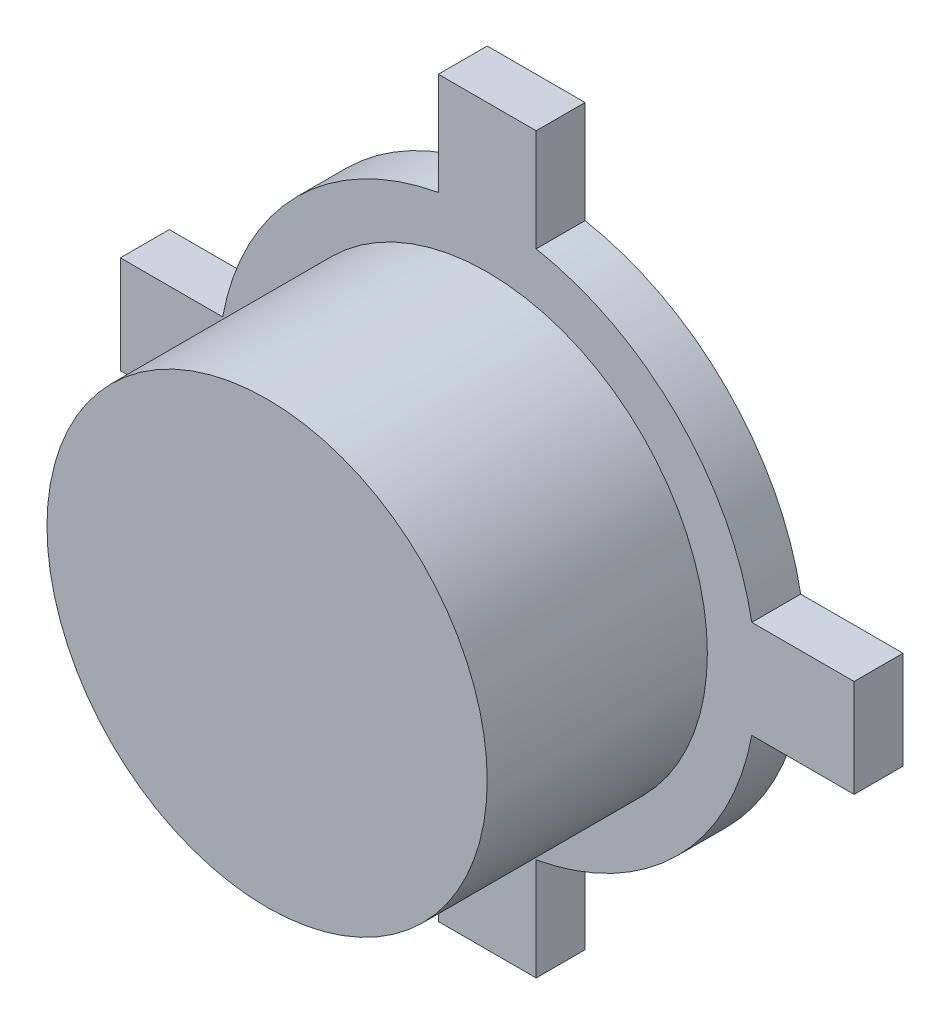
SolidWorks part; units mm, degrees
ref_plane "Front Plane" through (0, 0, 0) normal (0, 0, 1) x (1, 0, 0)
ref_plane "Top Plane" through (0, 0, 0) normal (0, 1, 0) x (1, 0, 0)
ref_plane "Right Plane" through (0, 0, 0) normal (1, 0, 0) x (0, 0, -1)
sketch "Sketch1" plane through (0, 0, 0) normal (0, 0, 1) x (1, 0, 0)
  circle A0 centre (0, 0) radius 4.5
  circle A1 centre (0, 0) radius 5 construction
  dimension "D1" = 0.5
extrude "Boss-Extrude1" add sketch "Sketch1" along normal blind 4.5
sketch "Sketch2" plane through (0, 0, 0) normal (0, 0, -1) x (-1, 0, 0)
  line L110 (-5.4083, 1) -> (-7.5, 1)
  line L111 (-7.5, 1) -> (-7.5, -1)
  line L112 (-7.5, -1) -> (-5.4083, -1)
  line L113 (-1, -5.4083) -> (-1, -7.5)
  line L114 (-1, -7.5) -> (1, -7.5)
  line L115 (1, -7.5) -> (1, -5.4083)
  line L116 (5.4083, -1) -> (7.5, -1)
  line L117 (7.5, -1) -> (7.5, 1)
  line L118 (7.5, 1) -> (5.4083, 1)
  line L119 (1, 5.4083) -> (1, 7.5)
  line L120 (-1, 7.5) -> (-1, 5.4083)
  line L121 (1, 7.5) -> (-1, 7.5)
  line L122 (-5.4083, 1) -> (-7.5, 1)
  line L123 (-7.5, 1) -> (-7.5, -1)
  line L124 (-7.5, -1) -> (-5.4083, -1)
  line L125 (-1, -5.4083) -> (-1, -7.5)
  line L126 (-1, -7.5) -> (1, -7.5)
  line L127 (1, -7.5) -> (1, -5.4083)
  line L128 (5.4083, -1) -> (7.5, -1)
  line L129 (7.5, -1) -> (7.5, 1)
  line L130 (7.5, 1) -> (5.4083, 1)
  line L131 (1, 5.4083) -> (1, 7.5)
  line L132 (-1, 7.5) -> (-1, 5.4083)
  line L133 (1, 7.5) -> (-1, 7.5)
  arc A42 (-5.4083, -1) -> (-1, -5.4083) centre (0, 0) ccw
  arc A43 (1, -5.4083) -> (5.4083, -1) centre (0, 0) ccw
  arc A44 (5.4083, 1) -> (1, 5.4083) centre (0, 0) ccw
  arc A45 (-1, 5.4083) -> (-5.4083, 1) centre (0, 0) ccw
  arc A46 (-5.4083, -1) -> (-1, -5.4083) centre (0, 0) ccw
  arc A47 (1, -5.4083) -> (5.4083, -1) centre (0, 0) ccw
  arc A48 (5.4083, 1) -> (1, 5.4083) centre (0, 0) ccw
  arc A49 (-1, 5.4083) -> (-5.4083, 1) centre (0, 0) ccw
  dimension "D1" = 0.5
extrude "Boss-Extrude2" add sketch "Sketch2" along normal blind 1
